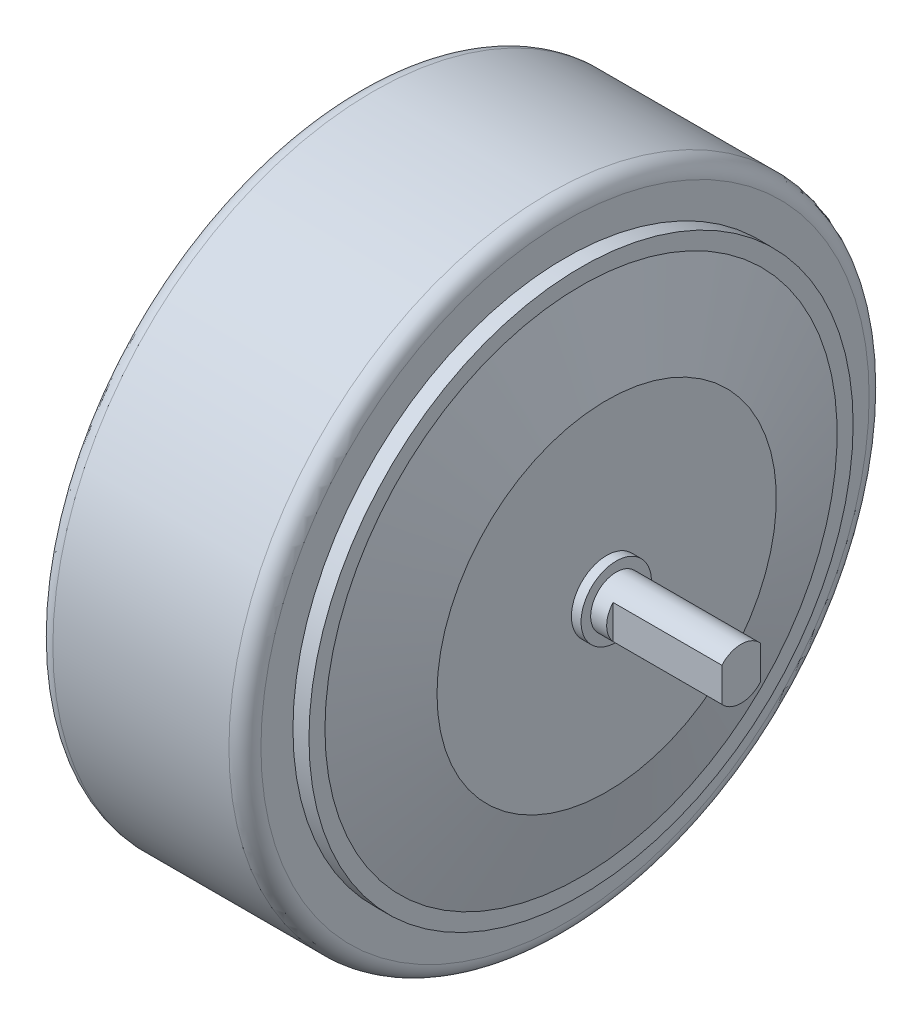
SolidWorks part; units mm, degrees
ref_plane "Спереди" through (0, 0, 0) normal (0, 0, 1) x (1, 0, 0)
ref_plane "Сверху" through (0, 0, 0) normal (0, 1, 0) x (1, 0, 0)
ref_plane "Справа" through (0, 0, 0) normal (1, 0, 0) x (0, 0, -1)
sketch "Эскиз1" plane through (0, 0, 0) normal (0, 0, 1) x (1, 0, 0)
  line L0 (-1100.9037, 0) -> (53944.2801, 0) construction
  line L1 (0, -1100.9037) -> (0, 53944.2801) construction
  line L2 (-32.5, 100) -> (32.5, 100)
  line L3 (32.5, 100) -> (32.5, 85)
  line L4 (32.5, 85) -> (37.5, 85)
  line L5 (37.5, 85) -> (37.5, 80)
  line L6 (37.5, 80) -> (45.5, 53)
  line L7 (45.5, 53) -> (45.5, 11)
  line L8 (45.5, 11) -> (48.5, 11)
  line L9 (48.5, 11) -> (48.5, 8)
  line L10 (48.5, 8) -> (87.5, 8)
  line L11 (87.5, 8) -> (87.5, 0)
  line L12 (-87.5, 8) -> (-87.5, 0)
  line L13 (-48.5, 8) -> (-87.5, 8)
  line L14 (-48.5, 11) -> (-48.5, 8)
  line L15 (-45.5, 11) -> (-48.5, 11)
  line L16 (-45.5, 53) -> (-45.5, 11)
  line L17 (-37.5, 80) -> (-45.5, 53)
  line L18 (-37.5, 85) -> (-37.5, 80)
  line L19 (-32.5, 85) -> (-37.5, 85)
  line L20 (-32.5, 100) -> (-32.5, 85)
  line L21 (87.5, 0) -> (-87.5, 0)
  point P19 (0, 100)
  dimension "D1" = 200
  dimension "D2" = 170
  dimension "D3" = 106
  dimension "D4" = 91
  dimension "D5" = 5
  dimension "D6" = 175
  dimension "D7" = 39
  dimension "D8" = 65
  dimension "D9" = 5
  dimension "D10" = 16
revolve "Повернуть1" add sketch "Эскиз1" angle 360 about L0
cosmetic thread "Условное изображение резьбы1" parameters "D2"=14.344
cosmetic thread "Условное изображение резьбы2" parameters "D2"=14.344
fillet "Скругление1" radius 5 2 edges at (32.5, 0, 100) (-32.5, 0, 100)
sketch "Эскиз2" plane through (0, 0, 0) normal (1, 0, 0) x (0, 0, -1)
  line L0 (-6, 5.2915) -> (-6, -5.2915)
  line L1 (6, 5.2915) -> (6, -5.2915)
  circle A0 centre (0, 0) radius 8 construction
  arc A1 (6, 5.2915) -> (-6, 5.2915) centre (0, 0) ccw
  arc A2 (-6, -5.2915) -> (6, -5.2915) centre (0, 0) ccw
  dimension "D1" = 12
ref_plane "Плоскость1" through (53.5, 0, 0) normal (1, 0, 0) x (0, 0, -1)
ref_plane "Плоскость2" through (-53.5, 0, 0) normal (-1, 0, 0) x (0, 0, 1)
extrude "Вырез-Вытянуть1" cut sketch "Эскиз2" against normal through all from surface flip side to cut starting at plane "Плоскость2"
extrude "Вырез-Вытянуть2" cut sketch "Эскиз2<2>" along normal through all from surface flip side to cut starting at plane "Плоскость1"
sketch "Эскиз2<2>" plane through (0, 0, 0) normal (1, 0, 0) x (0, 0, -1) same geometry as "Эскиз2"
sketch "Эскиз3" [suppressed] plane through (87.5, 0, 0) normal (1, 0, 0) x (0, 0, -1)
  circle A0 centre (0, 0) radius 53 construction
  circle A1 centre (0, 0) radius 53
extrude "Вырез-Вытянуть3" [suppressed] cut sketch "Эскиз3" against normal up to surface (42 mm away)
